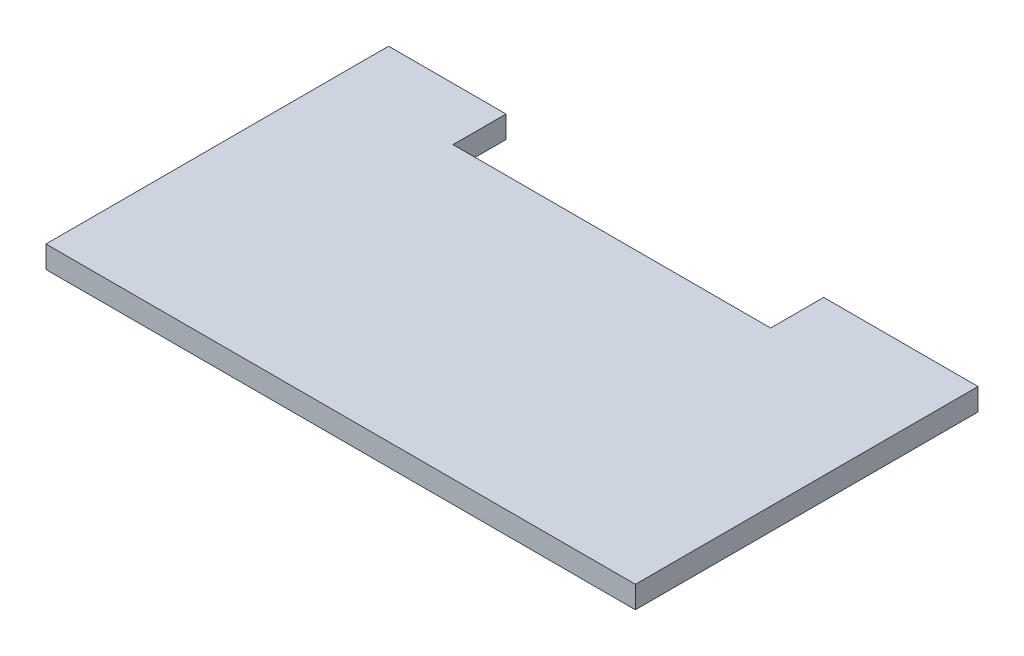
SolidWorks part; units mm, degrees
ref_plane "Front Plane" through (0, 0, 0) normal (0, 0, 1) x (1, 0, 0)
ref_plane "Top Plane" through (0, 0, 0) normal (0, 1, 0) x (1, 0, 0)
ref_plane "Right Plane" through (0, 0, 0) normal (1, 0, 0) x (0, 0, -1)
sketch "Sketch1" plane through (0, 0, 0) normal (0, 1, 0) x (1, 0, 0)
  line L0 (15.9432, 46.5) -> (15.9432, 39.3)
  line L1 (0, 0) -> (80, 0)
  line L2 (0, 0) -> (0, 46.5)
  line L3 (0, 46.5) -> (15.9432, 46.5)
  line L4 (80, 0) -> (80, 46.5)
  line L5 (15.9432, 39.3) -> (59.0568, 39.3)
  line L6 (59.0568, 39.3) -> (59.0568, 46.5)
  line L7 (80, 39.3) -> (0, 39.3) construction
  line L9 (59.0568, 46.5) -> (80, 46.5)
sketch "Sketch2" plane through (0, 0, 0) normal (0, 0, 1) x (1, 0, 0)
  line L1 (0, 0) -> (80, 0)
  line L2 (0, 0) -> (0, -3)
  line L3 (0, -3) -> (80, -3)
  line L4 (80, 0) -> (80, -3)
extrude "Boss-Extrude1" add sketch "Sketch1" against normal up to vertex (3 mm away) up to point (0, -3, 0)
